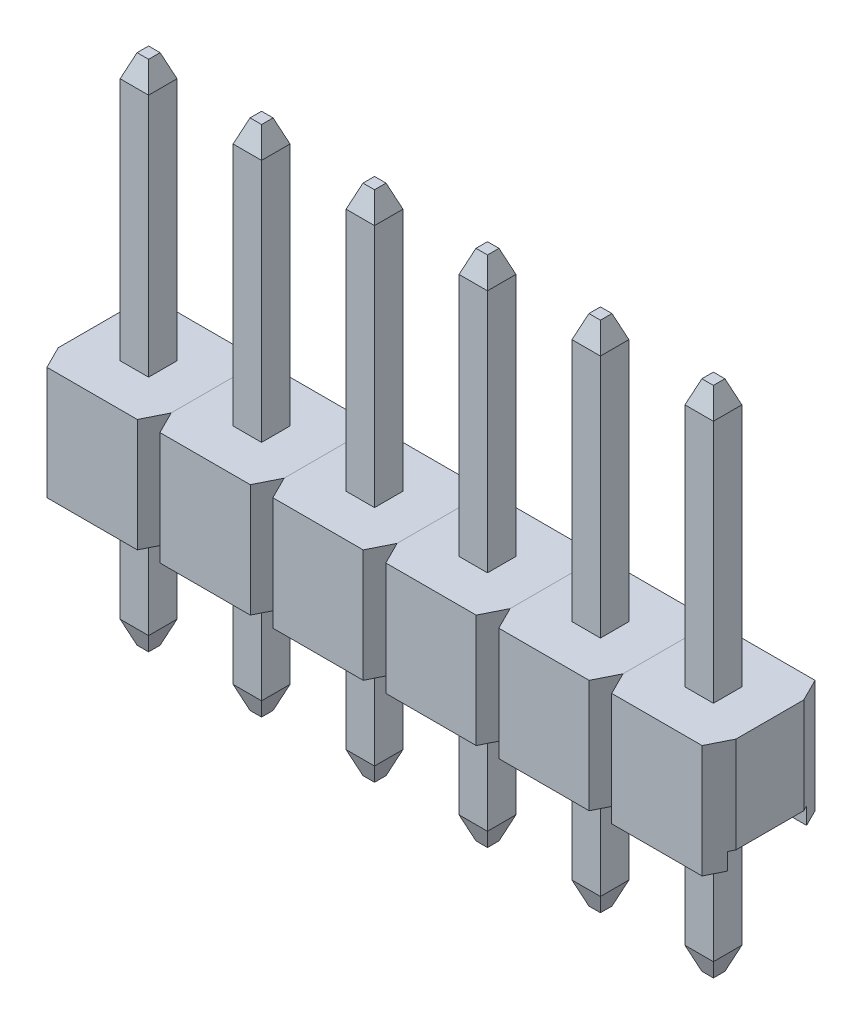
SolidWorks part; units mm, degrees
note: '?' marks a value the reader was unsure of.
ref_plane "Front Plane" through (0, 0, 0) normal (0, 0, 1) x (1, 0, 0)
ref_plane "Top Plane" through (0, 0, 0) normal (0, 1, 0) x (1, 0, 0)
ref_plane "Right Plane" through (0, 0, 0) normal (1, 0, 0) x (0, 0, -1)
sketch "Sketch1" plane through (0, 0, 0) normal (0, 1, 0) x (1, 0, 0)
  line L1 (0, 0) -> (2.54, 0)
  line L2 (0, 0) -> (0, 2.54)
  line L3 (0, 2.54) -> (2.54, 2.54)
  line L4 (2.54, 0) -> (2.54, 2.54)
  dimension "D1" = 2.54
  dimension "D2" = 2.54
extrude "Main Body" add sketch "Sketch1" along normal blind 2.54
sketch "Sketch3" plane through (0, 0, 0) normal (-1, 0, 0) x (0, 0, 1)
  line L0 (-2.54, 0) -> (0, 0) construction
  line L1 (-2.159, 0) -> (-0.381, 0)
  line L2 (-2.159, 0) -> (-2.159, 0.381)
  line L3 (-2.159, 0.381) -> (-0.381, 0.381)
  line L4 (-0.381, 0) -> (-0.381, 0.381)
  line L5 (-2.54, 0) -> (-2.159, 0) construction
  line L6 (-0.381, 0) -> (0, 0) construction
  dimension "D1" = 0.381
extrude "cut groove" cut sketch "Sketch3" against normal through all
sketch "SKETCH TOP POINT" plane through (0, 2.54, 0) normal (0, 1, 0) x (1, 0, 0)
  line L0 (0, 0) -> (2.54, 2.54) construction
  point P4 (1.27, 1.27)
sketch "SKETCH BOTTOM POINT" plane through (0, 0, 0) normal (0, -1, 0) x (1, 0, 0)
  point P0 (1.27, -1.27)
ref_axis "Axis1" through (1.27, 2.54, -1.27) along (0, -1, 0)?
sketch "Sketch4" plane through (0, 2.54, 0) normal (0, 1, 0) x (1, 0, 0)
  line L0 (0, 2.54) -> (0, 2.032)
  line L1 (0, 2.54) -> (0, 0) construction
  line L2 (0, 2.032) -> (0.254, 2.54)
  line L3 (2.54, 2.54) -> (0, 2.54) construction
  line L4 (0.254, 2.54) -> (0, 2.54)
  line L5 (2.54, 2.54) -> (2.286, 2.54)
  line L6 (2.286, 2.54) -> (2.54, 2.032)
  line L7 (2.54, 0) -> (2.54, 2.54) construction
  line L8 (2.54, 2.032) -> (2.54, 2.54)
  line L9 (2.54, 0) -> (2.286, 0)
  line L10 (0, 0) -> (2.54, 0) construction
  line L11 (2.286, 0) -> (2.54, 0.508)
  line L12 (2.54, 0.508) -> (2.54, 0)
  line L14 (0, 0) -> (0, 0.508)
  line L15 (0, 0.508) -> (0.254, 0)
  line L16 (0.254, 0) -> (0, 0)
  line M1 (0, 2.54) -> (0, 0)
  line M2 (0, 0) -> (2.54, 0)
  line M3 (2.54, 0) -> (2.54, 2.54)
  line M4 (2.54, 2.54) -> (0, 2.54)
  dimension "D1" = 0.254
  dimension "D2" = 0.508
extrude "cut corners" cut sketch "Sketch4" against normal through all contours L2 M1 M4 | L6 M4 M3 | L15 M1 M2 | L9 L11 L12
sketch "Sketch2" plane through (0, 2.54, 0) normal (0, 1, 0) x (1, 0, 0)
  line L0 (1.27, 2.54) -> (1.27, 1.59) construction
  line L1 (0.95, 0.95) -> (1.59, 0.95)
  line L2 (0.95, 0.95) -> (0.95, 1.59)
  line L3 (0.95, 1.59) -> (1.59, 1.59)
  line L4 (1.59, 0.95) -> (1.59, 1.59)
  line L6 (2.286, 2.54) -> (0.254, 2.54) construction
  line L8 (1.27, 0.95) -> (1.27, 0) construction
  line L9 (0.254, 0) -> (2.286, 0) construction
  dimension "D1" = 0.64
extrude "Pin" add sketch "Sketch2" along normal blind 6 and the other way offset from surface (5.54 mm away) 3 separate body other way up to face at (1.27, 0, -0.1905)
chamfer "Chamfer2" distance 0.1905 distance2 0.508 4 edges at (1.27, -3, -1.59) (1.59, -3, -1.27) (1.27, -3, -0.95) (0.95, -3, -1.27)
chamfer "Chamfer1" distance 0.508 distance2 0.1905 4 edges at (0.95, 8.54, -1.27) (1.27, 8.54, -1.59) (1.59, 8.54, -1.27) (1.27, 8.54, -0.95)
pattern_linear "pattern SLEEVE" count 6 spacing 2.54 along (-1, 0, 0) of "Main Body", "cut groove", "cut corners"
pattern_linear "pattern PINS" count 6 spacing 2.54 along (-1, 0, 0) of "Pin"
equation "\"pins\"= 6"
equation "\"D1@pattern SLEEVE\"=\"pins\""
equation "\"D1@pattern PINS\"=\"pins\""
